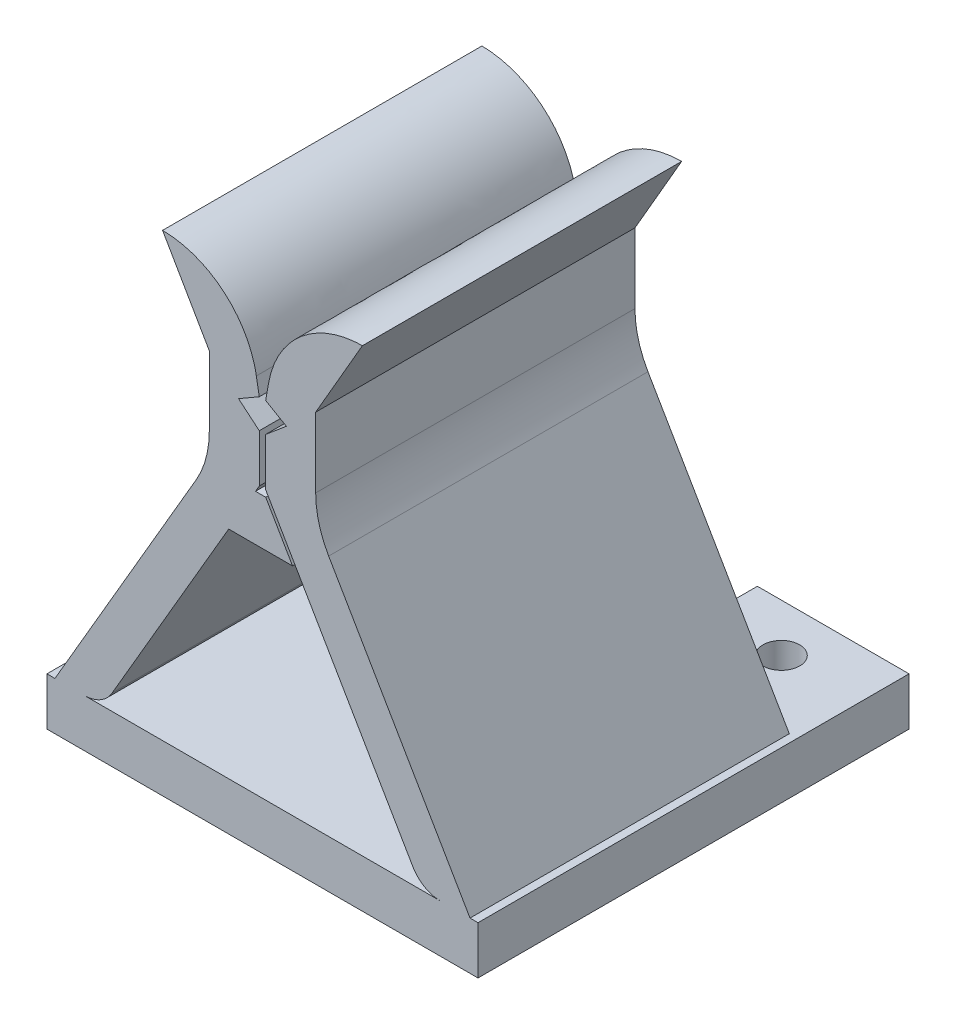
SolidWorks part; units mm, degrees
ref_plane "Piano frontale" through (0, 0, 0) normal (0, 0, 1) x (1, 0, 0)
ref_plane "Piano superiore" through (0, 0, 0) normal (0, 1, 0) x (1, 0, 0)
ref_plane "Piano destro" through (0, 0, 0) normal (1, 0, 0) x (0, 0, -1)
sketch "Schizzo1" plane through (0, 0, 0) normal (0, 0, 1) x (1, 0, 0)
  line L1 (0, 0) -> (50, 0)
  line L2 (0, 0) -> (0, 3)
  line L3 (0, 3) -> (50, 3)
  line L4 (50, 0) -> (50, 3)
  dimension "D1" = 50
  dimension "D2" = 3
extrude "Estrusione-Estrusione1" add sketch "Schizzo1" along normal blind 20
sketch "Schizzo2" plane through (0, 0, 20) normal (0, 0, 1) x (1, 0, 0)
  line L0 (25, 0) -> (25, 22.9285) construction
  line L1 (0, 0) -> (50, 0) construction
  line L2 (12, 3) -> (21.6677, 19.61)
  line L3 (50, 3) -> (0, 3) construction
  line L4 (21.6677, 19.61) -> (21.6677, 25.61)
  line L5 (21.6677, 25.61) -> (18.742, 30.6774)
  line L6 (18.742, 30.6774) -> (23.742, 30.6774)
  line L7 (12, 3) -> (15, 3)
  line L10 (23.742, 30.6774) -> (24.8, 24.6774)
  line L11 (24.8, 24.6774) -> (23.501, 23.9274)
  line L12 (23.501, 23.9274) -> (24.8, 22.8373)
  line L13 (26.499, 23.9274) -> (25.2, 22.8373)
  line L14 (25.2, 24.6774) -> (26.499, 23.9274)
  line L15 (26.258, 30.6774) -> (25.2, 24.6774)
  line L18 (38, 3) -> (35, 3)
  line L19 (31.258, 30.6774) -> (26.258, 30.6774)
  line L20 (28.3323, 25.61) -> (31.258, 30.6774)
  line L21 (28.3323, 19.61) -> (28.3323, 25.61)
  line L22 (38, 3) -> (28.3323, 19.61)
  line L23 (24.8, 22.8373) -> (24.8, 19.8373)
  line L24 (15, 3) -> (24.8, 19.8373)
  line L25 (35, 3) -> (25.2, 19.8373)
  line L26 (25.2, 22.8373) -> (25.2, 19.8373)
  dimension "D6" = 70
  dimension "D1" = 12
  dimension "D2" = 3
  dimension "D3" = 150
  dimension "D4" = 3
  dimension "D5" = 0.2
  dimension "D7" = 6
  dimension "D8" = 6
  dimension "D9" = 100
  dimension "D10" = 5
  dimension "D11" = 16.61
  dimension "D12" = 1.5
extrude "Estrusione-Estrusione2" add sketch "Schizzo2" against normal up to surface (20 mm away) separate body up to face at (25, 1.5, 0)
fillet "Raccordo2" radius 6 1 edges at (23.742, 30.6774, 10) first distance on face at (21.242, 30.6774, 10)
fillet "Raccordo3" radius 6 1 edges at (26.258, 30.6774, 10) first distance on face at (25.729, 27.6774, 10)
fillet "Raccordo4" radius 6 1 edges at (28.3323, 19.61, 10)
fillet "Raccordo5" radius 6 1 edges at (21.6677, 19.61, 10)
fillet "Raccordo7" radius 2 1 edges at (35, 3, 10)
fillet "Raccordo8" radius 2 1 edges at (15, 3, 10)
sketch "Schizzo5" plane through (0, 3, 0) normal (0, 1, 0) x (1, 0, 0)
  line L0 (50, -20) -> (0, -20) construction
  line L1 (0, 0) -> (11.5, 0)
  line L2 (0, 0) -> (0, -20)
  line L3 (0, -20) -> (11.5, -20)
  line L4 (11.5, 0) -> (11.5, -20)
  line L5 (12, 0) -> (12, -20) construction
  line L6 (25, -20) -> (25, 0) construction
  line L7 (50, 0) -> (0, 0) construction
  line L8 (38.5, 0) -> (38.5, -20)
  line L9 (50, -20) -> (38.5, -20)
  line L10 (50, 0) -> (50, -20)
  line L11 (50, 0) -> (38.5, 0)
  dimension "D1" = 0.5
extrude "Taglio-Estrusione2" cut sketch "Schizzo5" against normal up to surface (3 mm away) up to face at (25, 0, 10)
sketch "Schizzo9" plane through (0, 0, 20) normal (0, 0, 1) x (1, 0, 0)
  line L0 (24.5641, 19.432) -> (22.8843, 16.546)
  line L1 (15.5785, 3.9939) -> (24.8, 19.8373) construction
  line L2 (22.8843, 16.546) -> (26.8843, 16.546)
  line L3 (26.8843, 16.546) -> (25.2045, 19.432)
  line L4 (25.2045, 19.432) -> (24.5641, 19.432)
  line L7 (25.2, 19.8373) -> (34.4215, 3.9939) construction
  dimension "D1" = 4
  dimension "D2" = 0.2
  dimension "D3" = 0.6404
extrude "Estrusione-Estrusione7" add sketch "Schizzo9" against normal up to surface (20 mm away) up to face at (20.2418, 18.9106, 0)
sketch "Schizzo12" plane through (0, 3, 0) normal (0, 1, 0) x (1, 0, 0)
  line L0 (38.5, 0) -> (38.5, -20) construction
  line L1 (11.5, 0) -> (38.5, 0)
  line L2 (11.5, 0) -> (11.5, 7)
  line L3 (11.5, 7) -> (21, 7)
  line L4 (38.5, 0) -> (38.5, 7)
  line L8 (29, 7) -> (38.5, 7)
  line L9 (21, 7) -> (29, 7)
  circle A0 centre (16.5, 4) radius 1.15
  circle A1 centre (33.5, 4) radius 1.15
  dimension "D5" = 2.3
  dimension "D1" = 7
  dimension "D2" = 3
  dimension "D3" = 5
  dimension "D4" = 5
extrude "Estrusione-Estrusione9" add sketch "Schizzo12" against normal up to surface (3 mm away) up to face at (25, 0, 10)
sketch "Schizzo13" plane through (0, 3, 0) normal (0, 1, 0) x (1, 0, 0)
  line L0 (21, 4.032) -> (21, 7)
  line L1 (38.5, 7) -> (11.5, 7) construction
  line L2 (29, 4.032) -> (29, 7)
  arc A0 (21, 4.032) -> (29, 4.032) centre (25, 4.032) ccw
  circle A1 centre (16.5, 4) radius 1.15 construction
  dimension "D1" = 8
  dimension "D2" = 8.5
extrude "Taglio-Estrusione4" cut sketch "Schizzo13" against normal through all and the other way through all
